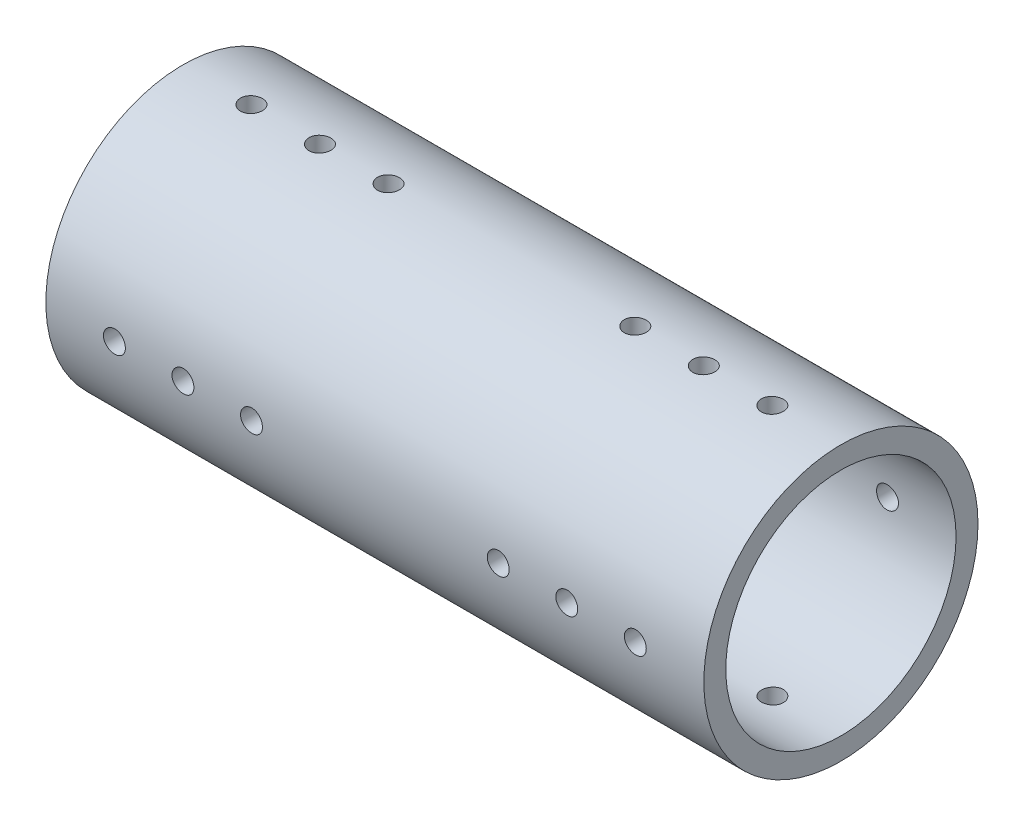
SolidWorks part; units mm, degrees
material "Zoltek Panex 33"
ref_plane "Спереди" through (0, 0, 0) normal (0, 0, 1) x (1, 0, 0)
ref_plane "Сверху" through (0, 0, 0) normal (0, 1, 0) x (1, 0, 0)
ref_plane "Справа" through (0, 0, 0) normal (1, 0, 0) x (0, 0, -1)
other "Configuration Table"
sketch "Эскиз2" plane through (0, 0, 0) normal (1, 0, 0) x (0, 0, -1)
  circle A0 centre (0, 0) radius 25
  circle A1 centre (0, 0) radius 21
  dimension "D1" = 50
  dimension "D2" = 42
extrude "Бобышка-Вытянуть2" add sketch "Эскиз2" along normal blind 120
ref_plane "Плоскость1" through (0, 0, 25) normal (0, 0, 1) x (1, 0, 0)
sketch "Эскиз4" plane through (0, 0, 25) normal (0, 0, 1) x (1, 0, 0)
  line L0 (0, -25) -> (120, -25) construction
  line L1 (120, -25) -> (120, 25) construction
  circle A0 centre (12.5, 0) radius 2
  circle A1 centre (107.5, 0) radius 2
  circle A2 centre (25, 0) radius 2
  circle A3 centre (37.5, 0) radius 2
  circle A4 centre (95, 0) radius 2
  circle A5 centre (82.5, 0) radius 2
  dimension "D1" = 4
  dimension "D4" = 4
  dimension "D6" = 4
  dimension "D8" = 4
  dimension "D10" = 4
  dimension "D11" = 4
  dimension "D2" = 12.5
  dimension "D3" = 25
  dimension "D5" = 12.5
  dimension "D7" = 12.5
  dimension "D9" = 12.5
  dimension "15" = 12.5
  dimension "D12" = 12.5
extrude "Вырез-Вытянуть2" cut sketch "Эскиз4" against normal through all and the other way blind 10 contours A0 | A1 | A2 | A3 | A5 | A4
pattern_circular "Круговой массив1" count 4 over 360 about axis through (120, 0, 0) along (-1, 0, 0) of "Вырез-Вытянуть2"
equation "\"Diameter\"= 50мм"
equation "\"D1@Эскиз2\"= \"Diameter\""
equation "\"Length\"= 120"
equation "\"Thickness\"= 4мм"
equation "\"D1@Бобышка-Вытянуть2\"= \"Length\""
equation "\"D2@Эскиз2\" = \"Diameter\" - \"Thickness\" * 2"
equation "\"D4@Эскиз4\"=\"D1@Эскиз4\""
equation "\"D5@Эскиз4\"=\"D2@Эскиз4\""
equation "\"D3@Эскиз4\"=\"Diameter\"/2"
equation "\"D6@Эскиз4\"=\"D1@Эскиз4\""
equation "\"D8@Эскиз4\"=\"D6@Эскиз4\""
equation "\"D10@Эскиз4\"=\"D4@Эскиз4\""
equation "\"D11@Эскиз4\"=\"D4@Эскиз4\""
equation "\"D9@Эскиз4\"=\"D7@Эскиз4\""
